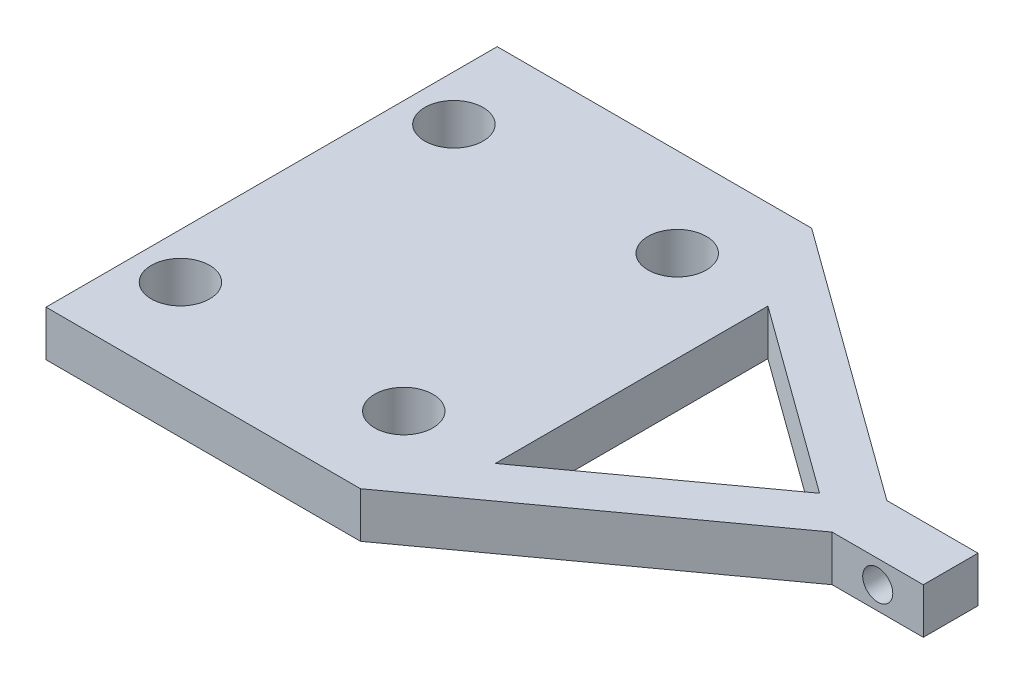
SolidWorks part; units mm, degrees
ref_plane "Front Plane" through (0, 0, 0) normal (0, 0, 1) x (1, 0, 0)
ref_plane "Top Plane" through (0, 0, 0) normal (0, 1, 0) x (1, 0, 0)
ref_plane "Right Plane" through (0, 0, 0) normal (1, 0, 0) x (0, 0, -1)
sketch "Sketch1" plane through (0, 0, 0) normal (0, 1, 0) x (1, 0, 0)
  line L1 (0, 0) -> (34.5, 0)
  line L2 (0, 0) -> (0, 49.5)
  line L3 (0, 49.5) -> (34.5, 49.5)
  line L4 (34.5, 0) -> (34.5, 49.5)
  dimension "D1" = 34.5
  dimension "D2" = 49.5
extrude "Boss-Extrude1" add sketch "Sketch1" along normal blind 5
sketch "Sketch2" plane through (0, 5, 0) normal (0, 1, 0) x (1, 0, 0)
  line L0 (34.5, 49.5) -> (0, 49.5) construction
  line L1 (0, 49.5) -> (0, 0) construction
  line L2 (17.25, 49.5) -> (17.25, 0) construction
  line L3 (0, 0) -> (34.5, 0) construction
  line L4 (0, 24.75) -> (17.25, 24.75) construction
  circle A0 centre (5, 39.75) radius 3.2
  circle A1 centre (5, 9.75) radius 3.2
  circle A2 centre (29.5, 9.75) radius 3.2
  circle A3 centre (29.5, 39.75) radius 3.2
  dimension "D1" = 6.4
  dimension "D3" = 5
  dimension "D2" = 9.75
extrude "Cut-Extrude1" cut sketch "Sketch2" against normal blind 5
sketch "Sketch3" plane through (0, 5, 0) normal (0, 1, 0) x (1, 0, 0)
  line L0 (17.25, 24.75) -> (181.75, 24.75) construction
  line L1 (189.75, 42.25) -> (34.5, 49.5)
  line L2 (189.75, 7.25) -> (34.5, 0)
  line L3 (189.75, 42.25) -> (189.75, 7.25)
  line L4 (171.0535, 14.3856) -> (89.0949, 10.5582)
  line L6 (171.0535, 35.1144) -> (89.0949, 38.9418)
  line L7 (34.5, 49.5) -> (34.5, 41.4913)
  line L8 (34.5, 0) -> (34.5, 49.5) construction
  line L9 (181.75, 34.6149) -> (34.1268, 41.5087) construction
  line L10 (34.5, 0) -> (34.5, 8.0087)
  line L11 (181.75, 14.8851) -> (34.1268, 7.9913) construction
  line L12 (84.0949, 39.1753) -> (84.0949, 10.3247)
  line L13 (89.0949, 38.9418) -> (89.0949, 10.5582)
  line L14 (89.0949, 39.1753) -> (89.0949, 10.3247) construction
  line L16 (0, 49.5) -> (0, 0) construction
  line L17 (0, 0) -> (34.5, 0) construction
  line L18 (84.0949, 39.1753) -> (34.5, 41.4913)
  line L19 (84.0949, 10.3247) -> (34.5, 8.0087)
  line L20 (171.0535, 35.1144) -> (171.0535, 14.3856)
  line L21 (181.75, 34.6149) -> (181.75, 14.8851) construction
  line L22 (178.13, 37.25) -> (184.13, 37.25)
  line L23 (178.13, 37.25) -> (178.13, 12.25)
  line L24 (178.13, 12.25) -> (184.13, 12.25)
  line L25 (184.13, 37.25) -> (184.13, 12.25)
  dimension "D1" = 17.5
  dimension "D4" = 17.25
  dimension "D5" = 24.75
  dimension "D6" = 17.5
  dimension "D7" = 172.5
  dimension "D8" = 25
  dimension "D9" = 12.5
  dimension "D10" = 6
  dimension "D11" = 5.62
  dimension "D2" = 8
  dimension "D3" = 5
extrude "Boss-Extrude2" add sketch "Sketch3" against normal blind 5
sketch "Sketch5" [suppressed] plane through (0, 5, 0) normal (0, 1, 0) x (1, 0, 0)
  line L0 (163.183, 43.1642) -> (163.183, 6.3358)
  line L1 (181.75, 42.25) -> (34.5, 49.5) construction
  line L2 (34.5, 0) -> (181.75, 7.25) construction
  line L3 (163.183, 6.3358) -> (181.75, 7.25)
  line L4 (181.75, 7.25) -> (181.75, 42.25)
  line L5 (181.75, 42.25) -> (163.183, 43.1642)
fillet "Fillet1" radius 10 6 edges at (89.0949, 2.5, -10.5582) (89.0949, 2.5, -38.9418) (84.0949, 2.5, -10.3247) (84.0949, 2.5, -39.1753) (34.5, 2.5, -41.4913) (34.5, 2.5, -8.0087)
fillet "Fillet2" radius 5 2 edges at (171.0535, 2.5, -14.3856) (171.0535, 2.5, -35.1144)
sketch "Sketch6" plane through (0, 5, 0) normal (0, 1, 0) x (1, 0, 0)
  line L1 (34.5, 49.5) -> (200.6847, 49.5)
  line L2 (34.5, 49.5) -> (34.5, 0)
  line L3 (34.5, 0) -> (200.6847, 0)
  line L4 (200.6847, 49.5) -> (200.6847, 0)
  line L5 (34.5, 49.5) -> (200.6847, 0) construction
  line L6 (34.5, 0) -> (200.6847, 49.5) construction
  point P4 (117.5923, 24.75)
extrude "Cut-Extrude3" cut sketch "Sketch6" against normal blind 10
sketch "Sketch7" plane through (0, 5, 0) normal (0, 1, 0) x (1, 0, 0)
  line L0 (64.5, 27.75) -> (34.5, 49.5)
  line L1 (74.5, 27.75) -> (64.5, 27.75)
  line L2 (74.5, 27.75) -> (74.5, 21.75)
  line L3 (74.5, 21.75) -> (64.5, 21.75)
  line L5 (74.5, 27.75) -> (64.5, 21.75) construction
  line L6 (74.5, 21.75) -> (64.5, 27.75) construction
  line L7 (34.5, 49.5) -> (34.5, 0)
  line L8 (34.5, 0) -> (64.5, 21.75)
  line L9 (64.5, 27.75) -> (64.5, 21.75)
  line L10 (69.5, 27.75) -> (69.5, 21.75)
  line L11 (60.1196, 24.75) -> (39.5, 39.6992)
  line L12 (39.5, 39.6992) -> (39.5, 9.8008)
  line L13 (39.5, 9.8008) -> (60.1196, 24.75)
  line L14 (61.5652, 23.7019) -> (39.5, 39.6992) construction
  line L15 (39.5, 9.8008) -> (61.5652, 25.7981) construction
  line L16 (0, 49.5) -> (0, 0) construction
  point P4 (69.5, 24.75)
  point P16 (74.5, 24.75)
  point P21 (0, 24.75)
  dimension "D1" = 6
  dimension "D3" = 30
  dimension "D4" = 10
  dimension "D5" = 0
  dimension "D2" = 5
extrude "Boss-Extrude3" add sketch "Sketch7" against normal up to surface (5 mm away) contours L11 L12 L13 | L0 L7 L8 L3 L2 L1 up to face at (17.25, 0, -24.75)
sketch "Sketch8" plane through (0, 0, -21.75) normal (0, 0, 1) x (1, 0, 0)
  line L0 (74.5, 0) -> (74.5, 5) construction
  circle A0 centre (69.5, 2.5) radius 1.65
  dimension "D1" = 3.3
  dimension "D2" = 5
extrude "Cut-Extrude4" cut sketch "Sketch8" against normal blind 10
